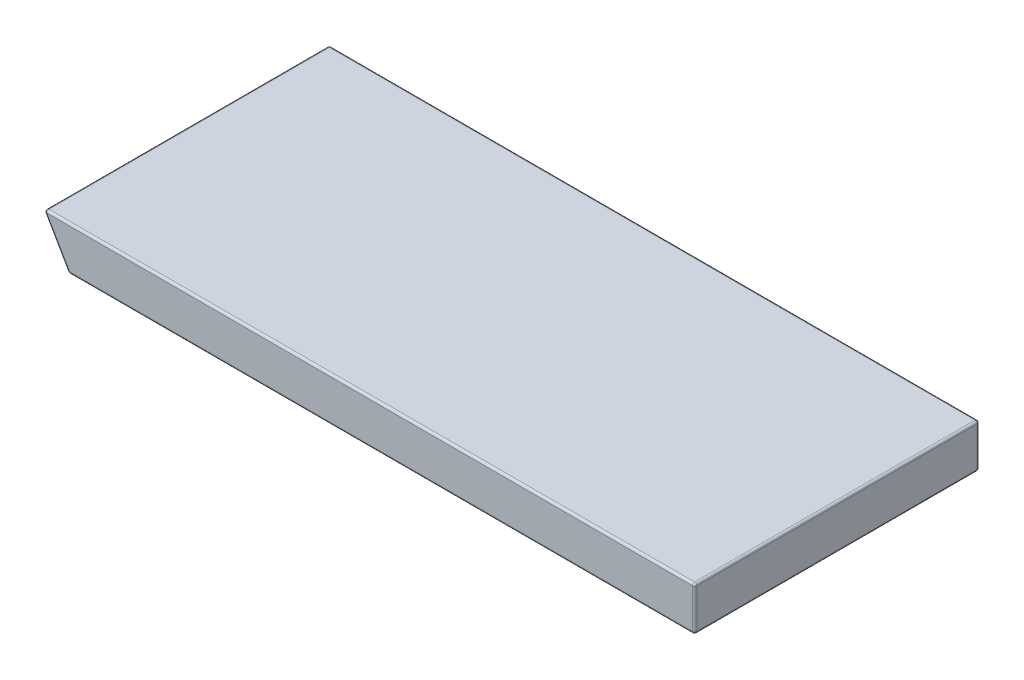
SolidWorks part; units mm, degrees
ref_plane "Front Plane" through (0, 0, 0) normal (0, 0, 1) x (1, 0, 0)
ref_plane "Top Plane" through (0, 0, 0) normal (0, 1, 0) x (1, 0, 0)
ref_plane "Right Plane" through (0, 0, 0) normal (1, 0, 0) x (0, 0, -1)
sketch "Sketch1" plane through (0, 0, 0) normal (0, 1, 0) x (1, 0, 0)
  line L1 (77, 32.5) -> (-77, 32.5)
  line L2 (77, 32.5) -> (77, -32.5)
  line L3 (77, -32.5) -> (-77, -32.5)
  line L4 (-77, 32.5) -> (-77, -32.5)
  line L5 (77, 32.5) -> (-77, -32.5) construction
  line L6 (77, -32.5) -> (-77, 32.5) construction
  point P0 (0, 0)
  dimension "D1" = 154
  dimension "D2" = 65
extrude "base" add sketch "Sketch1" along normal blind 10 contours L1 L4 L3 L2
sketch "Sketch2" plane through (0, 0, 0) normal (0, -1, 0) x (1, 0, 0)
  circle A0 centre (0, 0) radius 3
  dimension "D1" = 6
extrude "load cell button cut" [suppressed] cut sketch "Sketch2" against normal blind 2
sketch "Sketch4" plane through (0, 0, 0) normal (1, 0, 0) x (0, 0, -1)
  line L0 (3, 0) -> (3, 2)
  line L1 (3, 2) -> (0, 3.7321)
  line L2 (0, 3.7321) -> (0, 0) construction
  line L3 (0, 0) -> (3, 0)
  line L4 (0, 3.7321) -> (0, 0)
  dimension "D1" = 3
  dimension "D2" = 2
  dimension "D3" = 60
revolve "Cut-Revolve1" [suppressed] cut sketch "Sketch4" angle 360 about L2
sketch "Sketch5" plane through (0, 0, 32.5) normal (0, 0, 1) x (1, 0, 0)
  line L0 (-71.7735, 10) -> (-66, 0)
  line L1 (77, 0) -> (-77, 0) construction
  line L2 (-66, 0) -> (-66, 10) construction
  line L3 (77, 10) -> (-77, 10) construction
  line L5 (-77, 0) -> (-66, 0)
  dimension "D1" = 30
  dimension "D2" = 11
extrude "Cut-Extrude1" cut sketch "Sketch5" against normal through all
fillet "Fillet1" radius 0.5 12 edges at (77, 5, -32.5) (77, 5, 32.5) (2.6132, 10, -32.5) (2.6132, 10, 32.5) (77, 10, 0) (5.5, 0, -32.5) (5.5, 0, 32.5) (77, 0, 0) (-66, 0, 0) (-68.8868, 5, -32.5) (-71.7735, 10, 0) (-68.8868, 5, 32.5)
equation "\"D2@Sketch1\"=65"
equation "\"D1@Sketch1\"=144+10"
